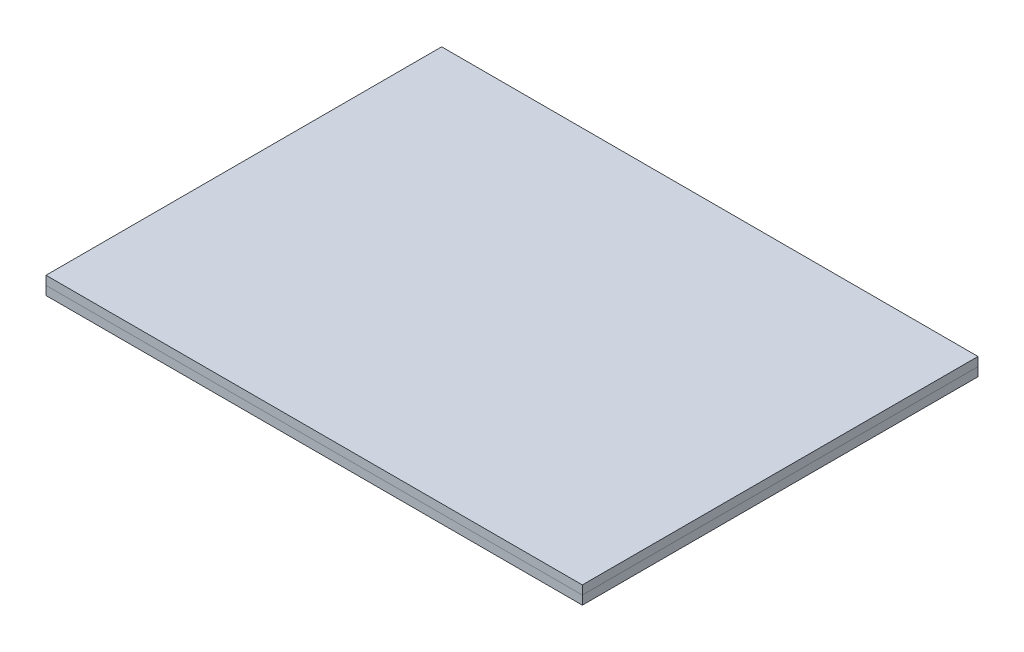
SolidWorks part; units mm, degrees
ref_plane "Front Plane" through (0, 0, 0) normal (0, 0, 1) x (1, 0, 0)
ref_plane "Top Plane" through (0, 0, 0) normal (0, 1, 0) x (1, 0, 0)
ref_plane "Right Plane" through (0, 0, 0) normal (1, 0, 0) x (0, 0, -1)
sketch "Sketch1" plane through (0, 0, 0) normal (0, 1, 0) x (1, 0, 0)
  line L1 (-27.5685, 15.0941) -> (33.4315, 15.0941)
  line L2 (-27.5685, 15.0941) -> (-27.5685, -29.9059)
  line L3 (-27.5685, -29.9059) -> (33.4315, -29.9059)
  line L4 (33.4315, 15.0941) -> (33.4315, -29.9059)
  dimension "D1" = 61
  dimension "D2" = 45
extrude "Boss-Extrude1" add sketch "Sketch1" along normal blind 1
extrude "Boss-Extrude3" add sketch "Sketch1<3>" along normal blind 1 from surface separate body starting at face at (2.9315, 1, 7.4059)
sketch "Sketch1<3>" plane through (0, 0, 0) normal (0, 1, 0) x (1, 0, 0) same geometry as "Sketch1"
